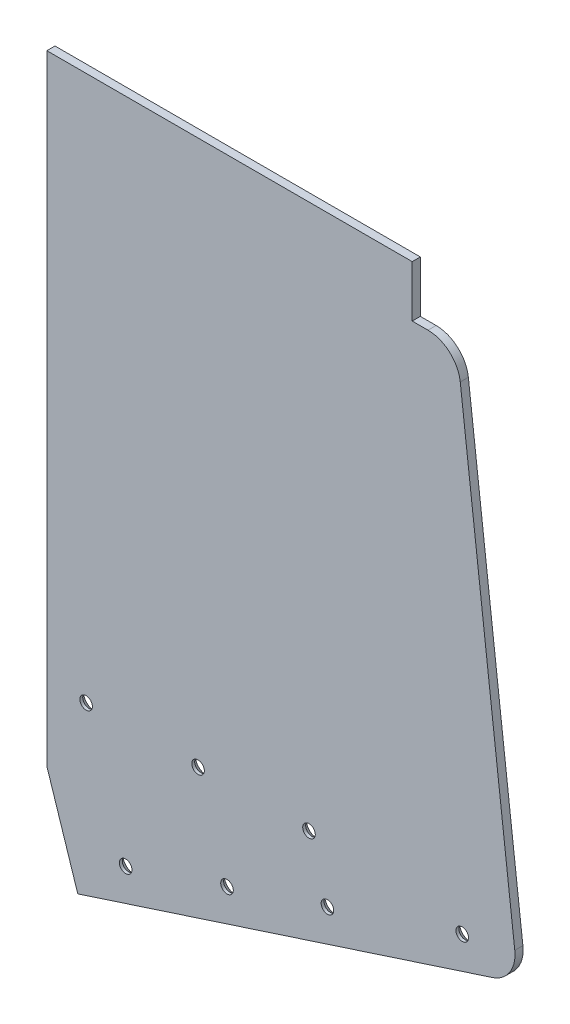
SolidWorks part; units mm, degrees
material "Acrylic (Medium-high impact)"
ref_plane "Front Plane" through (0, 0, 0) normal (0, 0, 1) x (1, 0, 0)
ref_plane "Top Plane" through (0, 0, 0) normal (0, 1, 0) x (1, 0, 0)
ref_plane "Right Plane" through (0, 0, 0) normal (1, 0, 0) x (0, 0, -1)
sketch "Sketch1" plane through (0, 0, 0) normal (0, 0, 1) x (1, 0, 0)
  line L1 (-234.753, 12.7) -> (-91.9973, 12.7)
  line L2 (-234.753, 12.7) -> (-234.753, -270.5428)
  line L3 (-234.753, -270.5428) -> (-50.7003, -210.6746)
  line L4 (-74.5335, -7.417) -> (-50.7003, -210.6746)
  line L5 (-64.9774, -197.966) -> (-88.1902, 0) construction
  line L8 (-74.5335, -7.417) -> (-91.9973, -7.417)
  line L9 (-91.9973, -7.417) -> (-91.9973, 12.7)
  line L10 (-91.9973, 0) -> (-91.9973, 12.7) construction
  dimension "D1" = 12.7
  dimension "D2" = 71.981
  dimension "D3" = 283.2428
extrude "Boss-Extrude1" add sketch "Sketch1" along normal blind 3.175
fillet "Fillet1" radius 12.7 2 edges at (-74.5335, -7.417, 1.5875) (-50.7003, -210.6746, 1.5875)
sketch "Sketch2" plane through (0, 0, 3.175) normal (0, 0, 1) x (1, 0, 0)
  line L0 (-234.753, -270.5428) -> (-60.5975, -213.8939) construction
  line L1 (-234.753, 12.7) -> (-234.753, -270.5428) construction
  line L2 (-234.753, -270.5428) -> (-222.6758, -266.6143)
  line L3 (-234.753, -229.4856) -> (-234.753, -270.5428)
  line L4 (-222.6758, -266.6143) -> (-234.753, -229.4856)
  dimension "D1" = 12.7
extrude "Cut-Extrude1" cut sketch "Sketch2" against normal through all
hole_wizard "CSK for #8 Flat Head Machine Screw1" positions "Sketch3" profile "Sketch4" countersink size "#8" standard "ANSI Inch" end condition through all
sketch "Sketch3" plane through (0, 0, 0) normal (0, 0, -1) x (-1, 0, 0)
  point P0 (203.9698, -247.917)
  point P3 (164.3688, -235.0357)
  point P6 (175.687, -200.2402)
  point P9 (219.4388, -200.3608)
  point P12 (125.1181, -222.2683)
  point P15 (132.3222, -200.1207)
  point P18 (72.4521, -205.1373)
sketch "Sketch4" plane through (-203.9698, -247.917, 0) normal (1, 0, 0) x (0, 1, 0)
  line L0 (0, 0) -> (0, 3.175)
  line L1 (0, 3.175) -> (2.4574, 3.175)
  line L2 (2.4574, 3.175) -> (2.4574, 2.0234)
  line L3 (2.4574, 2.0234) -> (4.2164, 0)
  line L5 (4.2164, 0) -> (0, 0)
  line L6 (-2.4574, 2.0234) -> (-4.2164, 0) construction
  line L11 (0, -6.35) -> (0, 107.95) construction
  dimension "Thru Hole Dia." = 4.9149
  dimension "Thru Hole Depth" = 3.175
  dimension "Near C'Sink Dia." = 8.4328
  dimension "Near C'Sink Angle" = 82
